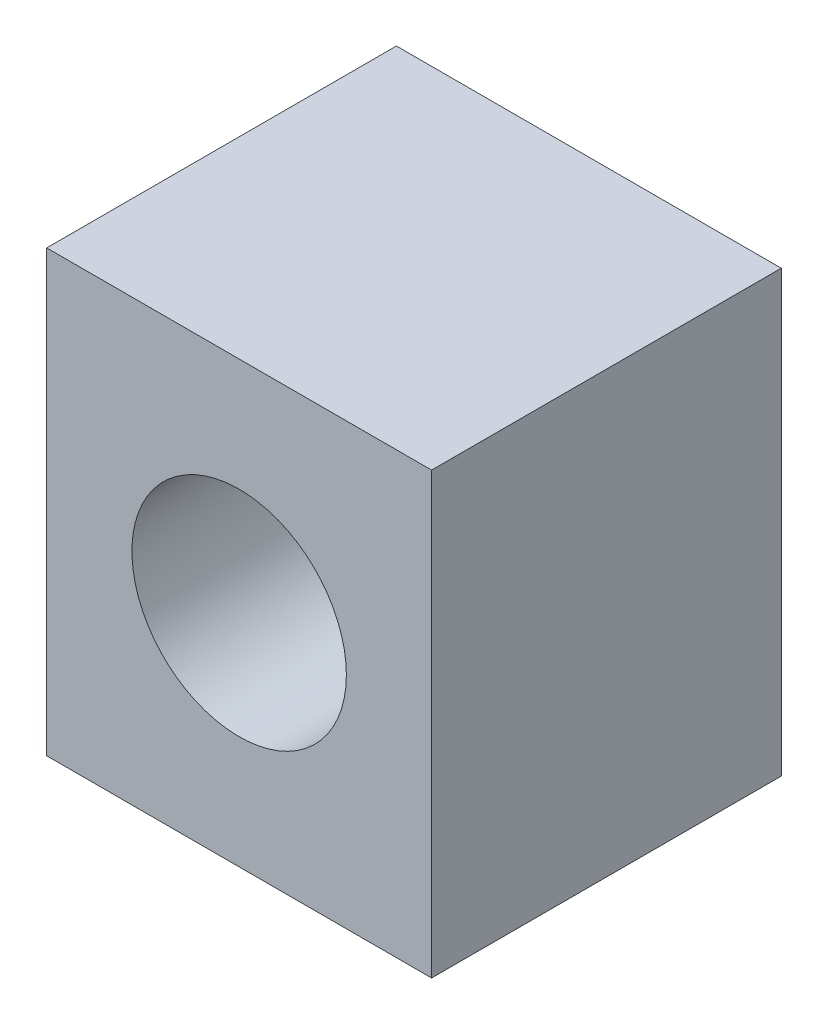
SolidWorks part; units mm, degrees
ref_plane "Front Plane" through (0, 0, 0) normal (0, 0, 1) x (1, 0, 0)
ref_plane "Top Plane" through (0, 0, 0) normal (0, 1, 0) x (1, 0, 0)
ref_plane "Right Plane" through (0, 0, 0) normal (1, 0, 0) x (0, 0, -1)
sketch "Sketch2" plane through (0, 0, 0) normal (0, 0, 1) x (1, 0, 0)
  line L5 (-1.75, 2) -> (1.75, 2)
  line L6 (-1.75, 2) -> (-1.75, -2)
  line L7 (-1.75, -2) -> (1.75, -2)
  line L8 (1.75, 2) -> (1.75, -2)
  line L9 (-1.75, 2) -> (1.75, -2) construction
  line L10 (-1.75, -2) -> (1.75, 2) construction
  point P0 (0, 0)
  dimension "D1" = 3.5
  dimension "D2" = 4
extrude "Boss-Extrude1" add sketch "Sketch2" along normal blind 3.18
sketch "Sketch3" plane through (0, 0, 3.18) normal (0, 0, 1) x (1, 0, 0)
  circle A2 centre (0, 0) radius 0.975
  dimension "D1" = 1.95
extrude "Cut-Extrude1" cut sketch "Sketch3" against normal through all
